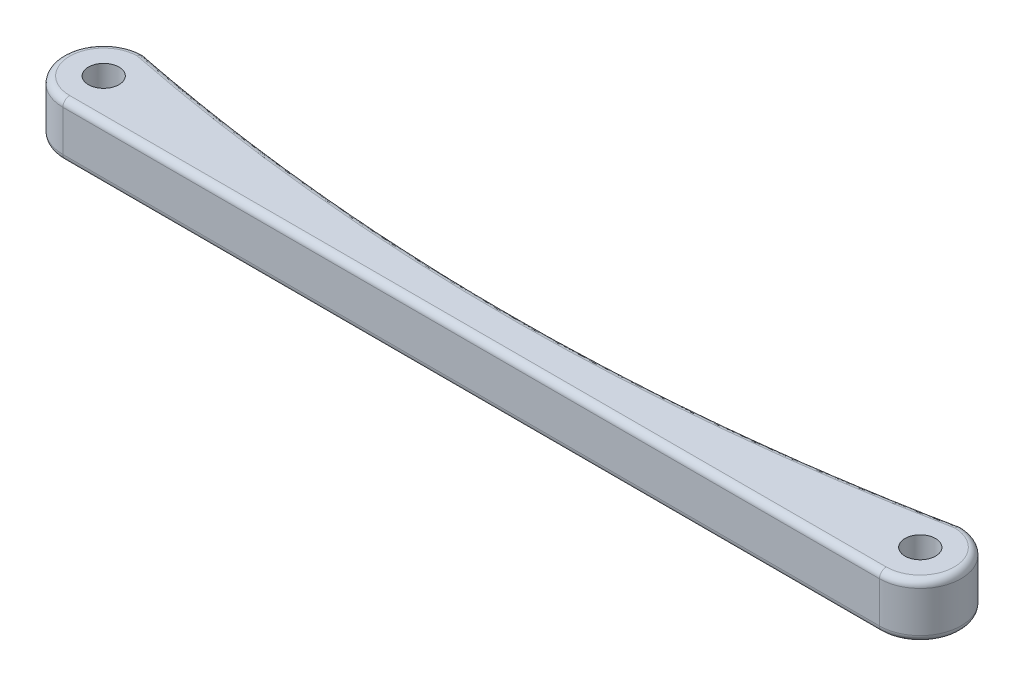
SolidWorks part; units mm, degrees
ref_plane "Front Plane" through (0, 0, 0) normal (0, 0, 1) x (1, 0, 0)
ref_plane "Top Plane" through (0, 0, 0) normal (0, 1, 0) x (1, 0, 0)
ref_plane "Right Plane" through (0, 0, 0) normal (1, 0, 0) x (0, 0, -1)
sketch "Sketch2" plane through (0, 0, 0) normal (0, 1, 0) x (1, 0, 0)
  line L0 (0, 0) -> (60, 0) construction
  line L1 (0, 3) -> (60, 3)
  line L2 (0, -3) -> (60, -3)
  arc A0 (0, 3) -> (0, -3) centre (0, 0) ccw
  arc A1 (60, -3) -> (60, 3) centre (60, 0) ccw
  circle A2 centre (0, 0) radius 1.125
  circle A3 centre (60, 0) radius 1.125
  point P3 (30, 0)
  dimension "D2" = 2.25
  dimension "D1" = 60
  dimension "D3" = 6
extrude "Boss-Extrude1" add sketch "Sketch2" along normal blind 4
sketch "Sketch3" plane through (0, 4, 0) normal (0, 1, 0) x (1, 0, 0)
  line L0 (60, 3) -> (0, 3) construction
  line L1 (0, 3) -> (60, 3)
  spline S0 degree 2 poles (0, 3) (30, -3) (60, 3) knots 0 0 0 1 1 1
  point P8 (30, 3)
extrude "Cut-Extrude1" cut sketch "Sketch3" against normal through all both and the other way through all
fillet "Fillet2" radius 0.5 10 edges at (63, 0, 0) (30, 0, 3) (63, 4, 0) (30, 4, 3) (-3, 0, 0) (-3, 4, 0) (60, 2, -3) (0, 2, -3)
